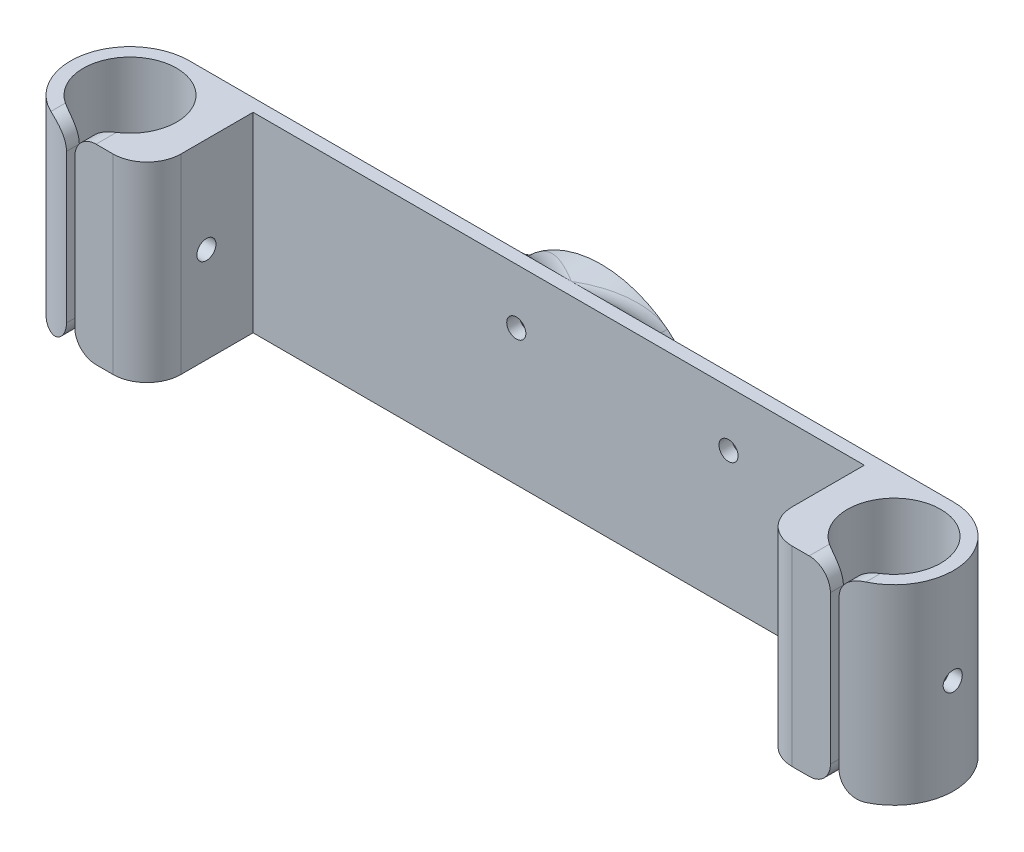
SolidWorks part; units mm, degrees
ref_plane "Front Plane" through (0, 0, 0) normal (0, 0, 1) x (1, 0, 0)
ref_plane "Top Plane" through (0, 0, 0) normal (0, 1, 0) x (1, 0, 0)
ref_plane "Right Plane" through (0, 0, 0) normal (1, 0, 0) x (0, 0, -1)
sketch "Sketch1" plane through (0, 0, 0) normal (0, 1, 0) x (1, 0, 0)
  line L0 (137.4606, -14.5) -> (119.4606, -14.5)
  line L1 (119.4606, -14.5) -> (119.4606, 10.5)
  line L2 (-42.5394, -14.5) -> (-24.5394, -14.5)
  line L3 (-42.5394, 13.5) -> (137.4606, 13.5)
  line L4 (119.4606, 10.5) -> (-24.5394, 10.5)
  line L5 (-24.5394, -14.5) -> (-24.5394, 10.5)
  circle A0 centre (-42.5394, -0.5) radius 11
  circle A1 centre (137.4606, -0.5) radius 11
  arc A2 (-42.5394, -14.5) -> (-42.5394, 13.5) centre (-42.5394, -0.5) cw
  arc A6 (137.4606, 13.5) -> (137.4606, -14.5) centre (137.4606, -0.5) cw
  dimension "D3" = 22
  dimension "D4" = 22
  dimension "D5" = 180
  dimension "D6" = 3
  dimension "D1" = 18
  dimension "D2" = 18
  dimension "D8" = 3
extrude "Boss-Extrude1" add sketch "Sketch1" along normal blind 45
fillet "Fillet1" radius 8 2 edges at (119.4606, 22.5, 14.5) (-24.5394, 22.5, 14.5)
sketch "Sketch2" plane through (0, 0, -10.5) normal (0, 0, 1) x (1, 0, 0)
  line L0 (119.4606, 32) -> (87.4606, 32) construction
  line L1 (119.4606, 45) -> (119.4606, 0) construction
  line L2 (87.4606, 32) -> (37.4606, 32) construction
  line L5 (137.4606, 0) -> (-42.5394, 0) construction
  circle A0 centre (87.4606, 32) radius 2.25
  circle A1 centre (37.4606, 32) radius 2.25
  dimension "D4" = 4.5
  dimension "D5" = 4.5
  dimension "D1" = 32
  dimension "D2" = 50
  dimension "D3" = 32
extrude "Cut-Extrude1" cut sketch "Sketch2" against normal blind 10
sketch "Sketch5" plane through (0, 0, 14.5) normal (0, 0, 1) x (1, 0, 0)
  line L0 (-42.5394, 45) -> (-42.5394, 0)
  line L1 (137.4606, 45) -> (137.4606, 0)
extrude "Cut-Extrude-Thin1" cut sketch "Sketch5" against normal blind 10 thin thin type mid plane wall 2
fillet "Fillet3" radius 5 8 edges at (138.4606, 0, 12.9593) (136.4606, 0, 12.9772) (138.4606, 45, 12.9593) (136.4606, 45, 12.9772) (-41.5394, 45, 12.9772) (-43.5394, 45, 12.9593) (-43.5394, 0, 12.9593) (-41.5394, 0, 12.9772)
sketch "Sketch7" plane through (-24.5394, 0, 0) normal (1, 0, 0) x (0, 0, -1)
  line L0 (-0.5, 45) -> (-0.5, 0) construction
  line L1 (-6.5, 45) -> (10.5, 45) construction
  line L2 (-6.5, 0) -> (10.5, 0) construction
  circle A0 centre (-0.5, 22.5) radius 2.25
  dimension "D2" = 4.5
  dimension "D1" = 11
ref_plane "Plane1" through (47.4606, 0, 0) normal (1, 0, 0) x (0, 0, -1)
extrude "Cut-Extrude6" cut sketch "Sketch7" against normal through all both and the other way through all
sketch "Sketch9" plane through (0, 0, -13.5) normal (0, 0, -1) x (-1, 0, 0)
  line L0 (-47.4606, 45) -> (-47.4606, 20) construction
  line L1 (-137.4606, 45) -> (42.5394, 45) construction
  line L4 (-24.9606, 20) -> (-24.9606, 0)
  line L5 (-137.4606, 0) -> (42.5394, 0) construction
  line L6 (-24.9606, 0) -> (-22.4606, 0)
  line L7 (-22.4606, 0) -> (-22.4606, 20)
  line L8 (-69.9606, 20) -> (-69.9606, 0)
  line L9 (-69.9606, 0) -> (-72.4606, 0)
  line L10 (-72.4606, 0) -> (-72.4606, 20)
  arc A0 (-24.9606, 20) -> (-69.9606, 20) centre (-47.4606, 20) ccw
  arc A1 (-22.4606, 20) -> (-72.4606, 20) centre (-47.4606, 20) ccw
  dimension "D1" = 45
  dimension "D2" = 2.5
extrude "Boss-Extrude2" add sketch "Sketch9" along normal blind 4
sketch "Sketch10" plane through (0, 0, -17.5) normal (0, 0, -1) x (-1, 0, 0)
  line L6 (-64.9606, 0) -> (-64.9606, 20)
  line L7 (-29.9606, 20) -> (-29.9606, 0)
  line L8 (-69.9606, 0) -> (-64.9606, 0)
  line L9 (-29.9606, 0) -> (-24.9606, 0)
  line L12 (-24.9606, 0) -> (-22.4606, 0)
  line L13 (-22.4606, 0) -> (-22.4606, 20)
  line L14 (-72.4606, 20) -> (-72.4606, 0)
  line L15 (-72.4606, 0) -> (-69.9606, 0)
  line L16 (-69.9606, 0) -> (-69.9606, 20)
  line L17 (-24.9606, 20) -> (-24.9606, 0)
  line L18 (-24.9606, 0) -> (-22.4606, 0)
  line L19 (-22.4606, 0) -> (-22.4606, 20)
  line L20 (-72.4606, 20) -> (-72.4606, 0)
  line L21 (-72.4606, 0) -> (-69.9606, 0)
  arc A2 (-29.9606, 20) -> (-64.9606, 20) centre (-47.4606, 20) ccw
  arc A4 (-22.4606, 20) -> (-72.4606, 20) centre (-47.4606, 20) ccw
  arc A5 (-24.9606, 20) -> (-69.9606, 20) centre (-47.4606, 20) ccw
  arc A6 (-22.4606, 20) -> (-72.4606, 20) centre (-47.4606, 20) ccw
  dimension "D1" = 0
extrude "Boss-Extrude3" add sketch "Sketch10" along normal blind 3
fillet "Fillet4" radius 7 4 edges at (72.4606, 10, -13.5) (65.1383, 37.6777, -13.5) (29.7829, 37.6777, -13.5) (22.4606, 10, -13.5)
